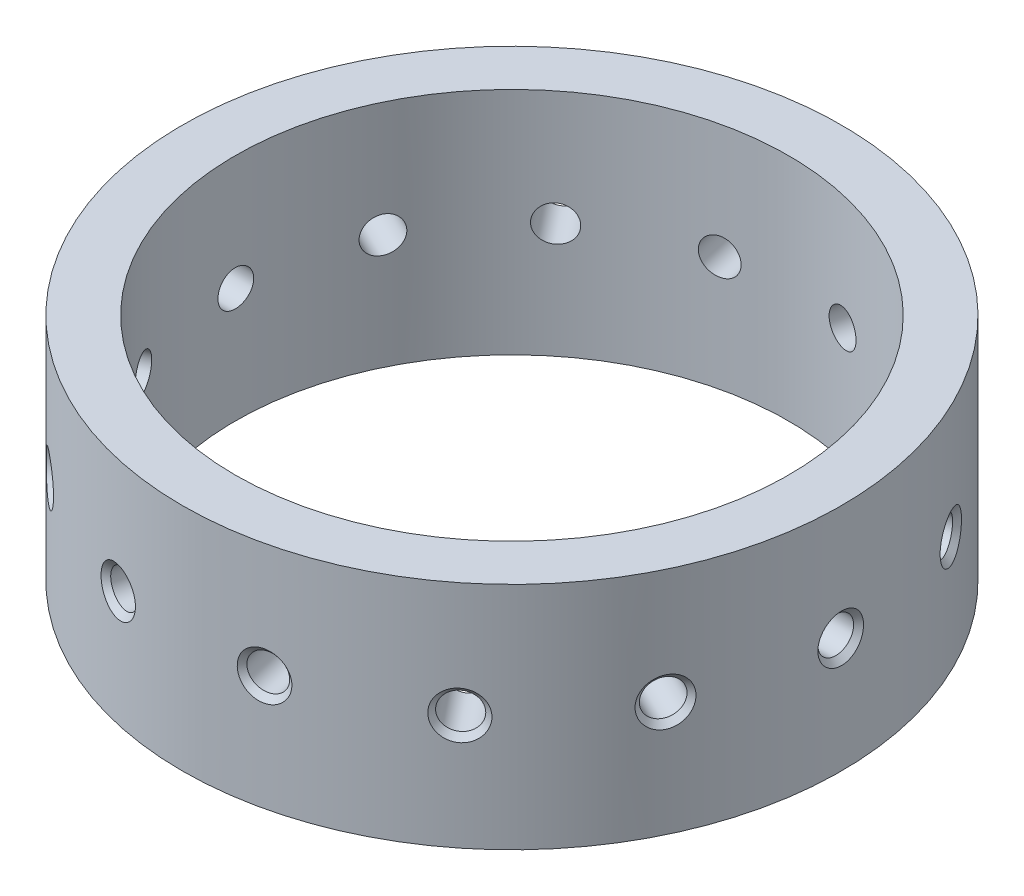
SolidWorks part; units mm, degrees
material "6061-T6 (SS)"
ref_plane "Front Plane" through (0, 0, 0) normal (0, 0, 1) x (1, 0, 0)
ref_plane "Top Plane" through (0, 0, 0) normal (0, 1, 0) x (1, 0, 0)
ref_plane "Right Plane" through (0, 0, 0) normal (1, 0, 0) x (0, 0, -1)
sketch "Sketch1" plane through (0, 0, 0) normal (0, 0, 1) x (1, 0, 0)
  line L0 (0, 0) -> (0, -26301.4581) construction
  line L1 (32.5, 0) -> (60, 0)
  line L2 (60, 0) -> (60, 3)
  line L3 (60, 3) -> (57, 3)
  line L4 (57, 3) -> (57, 4)
  line L5 (57, 4) -> (38.71, 4)
  line L6 (38.71, 4) -> (38.71, 27)
  line L7 (38.71, 27) -> (32.5, 27)
  line L8 (32.5, 27) -> (32.5, 0)
  dimension "D1" = 77.42
  dimension "D2" = 65
  dimension "D3" = 120
  dimension "D4" = 114
  dimension "D5" = 3
  dimension "D6" = 1
  dimension "D7" = 23
revolve "Revolve1" add sketch "Sketch1" angle 360 about L0
hole_wizard "M5 Tapped Hole1" positions "3DSketch1" profile "Sketch2" tap size "M5" standard "ISO" end condition up to next
sketch3d "3DSketch1"
  point P0 (38.71, 13.5, 0)
  dimension "D1" = 9.5
sketch "Sketch2" plane through (38.71, 13.5, 0) normal (0, 1, 0) x (0, 0, -1)
  line L0 (0, 0) -> (0, 6.21)
  line L1 (0, 6.21) -> (2.1, 6.21)
  line L2 (2.1, 6.21) -> (2.1, 0.675)
  line L3 (2.1, 0.675) -> (2.775, 0)
  line L5 (2.775, 0) -> (0, 0)
  line L6 (-2.1, 0.675) -> (-2.775, 0) construction
  line L11 (0, -6.35) -> (0, 107.95) construction
  dimension "Thru Tap Drill Dia." = 4.2
  dimension "Thru Tap Drill Depth" = 6.21
  dimension "Near C'Sink Dia." = 5.55
  dimension "Near C'Sink Angle" = 90
cosmetic thread "Hole Thread1" parameters "D2"=5
pattern_circular "CirPattern1" count 14 over 360 about axis through (0, 0, 0) along (0, 1, 0) of "M5 Tapped Hole1" reverse direction yes
cosmetic thread "Hole Thread2" parameters "D2"=5
cosmetic thread "Hole Thread3" parameters "D2"=5
cosmetic thread "Hole Thread4" parameters "D2"=5
cosmetic thread "Hole Thread5" parameters "D2"=5
cosmetic thread "Hole Thread6" parameters "D2"=5
cosmetic thread "Hole Thread7" parameters "D2"=5
cosmetic thread "Hole Thread8" parameters "D2"=5
cosmetic thread "Hole Thread9" parameters "D2"=5
cosmetic thread "Hole Thread10" parameters "D2"=5
cosmetic thread "Hole Thread11" parameters "D2"=5
cosmetic thread "Hole Thread12" parameters "D2"=5
cosmetic thread "Hole Thread13" parameters "D2"=5
cosmetic thread "Hole Thread14" parameters "D2"=5
sketch "Sketch3" plane through (0, 0, 0) normal (0, 0, 1) x (1, 0, 0)
  line L0 (66, 0) -> (-66, 0) construction
  line L1 (38.71, 4) -> (60, 4)
  line L2 (38.71, 4) -> (38.71, 0)
  line L3 (38.71, 0) -> (60, 0)
  line L4 (60, 4) -> (60, 0)
  line L5 (-60, 0) -> (60, 0) construction
  line L6 (0, 0) -> (0, -50000) construction
revolve "Cut-Revolve1" cut sketch "Sketch3" angle 360 about L6
equation "\"CanSat_Len\"= 400mm"
equation "\"CanSat_Dia\"= 150mm"
equation "\"BodyTube_ID\"= 114mm"
equation "\"BodyTube_OD\"= 120mm"
equation "\"PayLoadBay_ID\"= 164mm"
equation "\"PayLoadBay_OD\"= 170mm"
equation "\"ParachuteBay_Pitch\"= 400mm"
equation "\"ElectronicsTray_PitchDist\"= 50mm"
equation "\"ElectronicsTray_Height\"= 140mm"
equation "\"MotorDia\"= 98mm"
equation "\"MotorLen\"=289mm"
equation "\"D3@Sketch1\"=\"BodyTube_OD\""
equation "\"D4@Sketch1\"=\"BodyTube_ID\""
